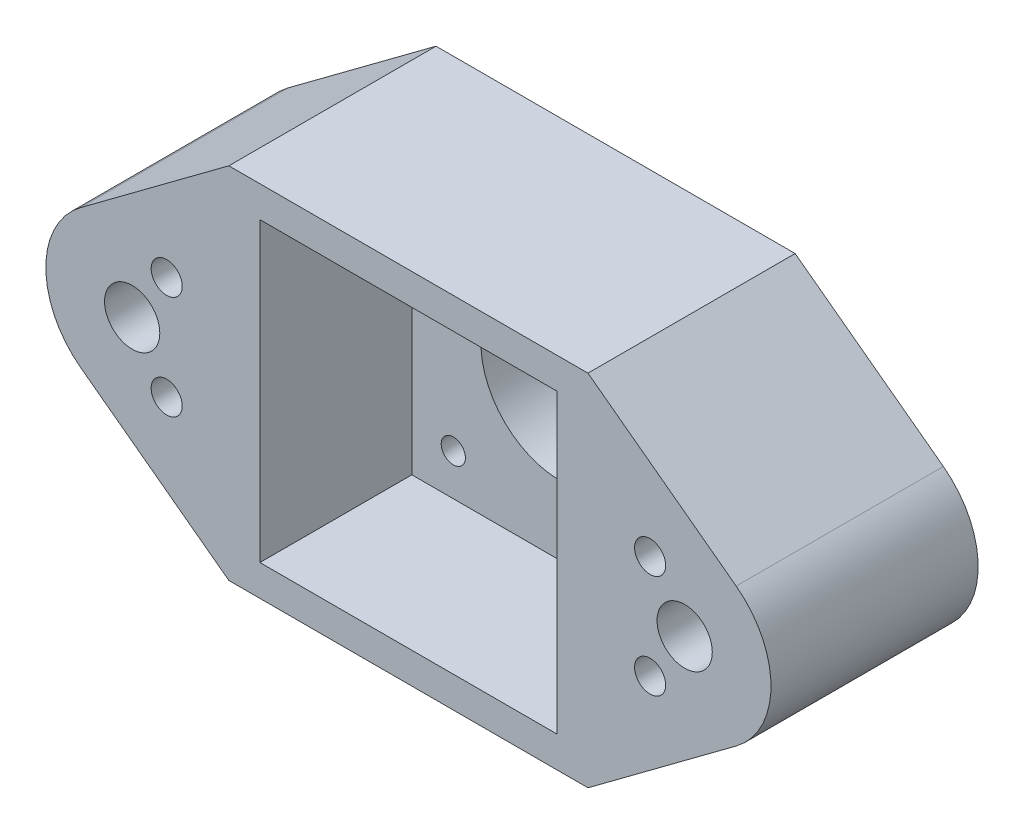
SolidWorks part; units mm, degrees
ref_plane "Plano frontal" through (0, 0, 0) normal (0, 0, 1) x (1, 0, 0)
ref_plane "Plano superior" through (0, 0, 0) normal (0, 1, 0) x (1, 0, 0)
ref_plane "Plano direito" through (0, 0, 0) normal (1, 0, 0) x (0, 0, -1)
sketch "Esboço1" plane through (0, 0, 0) normal (0, 0, 1) x (1, 0, 0)
  line L0 (-40, 0) -> (40, 0) construction
  line L1 (-15.5, -15.5) -> (15.5, -15.5) construction
  line L2 (-15.5, -15.5) -> (-15.5, 15.5) construction
  line L3 (-15.5, 15.5) -> (15.5, 15.5) construction
  line L4 (15.5, -15.5) -> (15.5, 15.5) construction
  line L5 (-15.5, -15.5) -> (15.5, 15.5) construction
  line L6 (-15.5, 15.5) -> (15.5, -15.5) construction
  line L7 (-26, 26) -> (26, 26)
  line L9 (-26, -26) -> (26, -26)
  line L11 (-26, 26) -> (26, -26) construction
  line L12 (-26, -26) -> (26, 26) construction
  line L13 (-26, 26) -> (-47.4626, 10.0279)
  line L14 (-26, -26) -> (-47.4626, -10.0279)
  line L15 (0, 33.9492) -> (0, -26.7365) construction
  line L16 (26, 26) -> (47.4626, 10.0279)
  line L18 (47.4626, -10.0279) -> (26, -26)
  circle A0 centre (-15.5, 15.5) radius 1.75
  circle A1 centre (15.5, 15.5) radius 1.75
  circle A2 centre (15.5, -15.5) radius 1.75
  circle A3 centre (-15.5, -15.5) radius 1.75
  circle A4 centre (0, 0) radius 11.5
  circle A5 centre (-40, 0) radius 4
  circle A6 centre (40, 0) radius 4
  arc A7 (-47.4626, 10.0279) -> (-47.4626, -10.0279) centre (-40, 0) ccw
  arc A8 (47.4626, -10.0279) -> (47.4626, 10.0279) centre (40, 0) ccw
  circle A9 centre (-35, 7.5) radius 2.25
  circle A10 centre (-35, -7.5) radius 2.25
  circle A11 centre (35, -7.5) radius 2.25
  circle A12 centre (35, 7.5) radius 2.25
  point P0 (0, 0)
  point P10 (0, 0)
  point P21 (0, 0)
  point P39 (0, 26)
  dimension "D2" = 3.5
  dimension "D3" = 23
  dimension "D6" = 8
  dimension "D7" = 25
  dimension "D9" = 4.5
  dimension "D1" = 31
  dimension "D4" = 52
  dimension "D5" = 80
  dimension "D8" = 15
  dimension "D10" = 35
  dimension "D11" = 52
extrude "Ressalto-extrusão1" add sketch "Esboço1" along normal blind 30
sketch "Esboço2" plane through (0, 0, 30) normal (0, 0, 1) x (1, 0, 0)
  line L1 (-21.5, 21.5) -> (21.5, 21.5)
  line L2 (-21.5, 21.5) -> (-21.5, -21.5)
  line L3 (-21.5, -21.5) -> (21.5, -21.5)
  line L4 (21.5, 21.5) -> (21.5, -21.5)
  line L5 (-21.5, 21.5) -> (21.5, -21.5) construction
  line L6 (-21.5, -21.5) -> (21.5, 21.5) construction
  point P0 (0, 0)
  dimension "D1" = 43
extrude "Corte-extrusão1" cut sketch "Esboço2" against normal blind 22
equation "\"D11@Esboço1\"=\"D4@Esboço1\""
